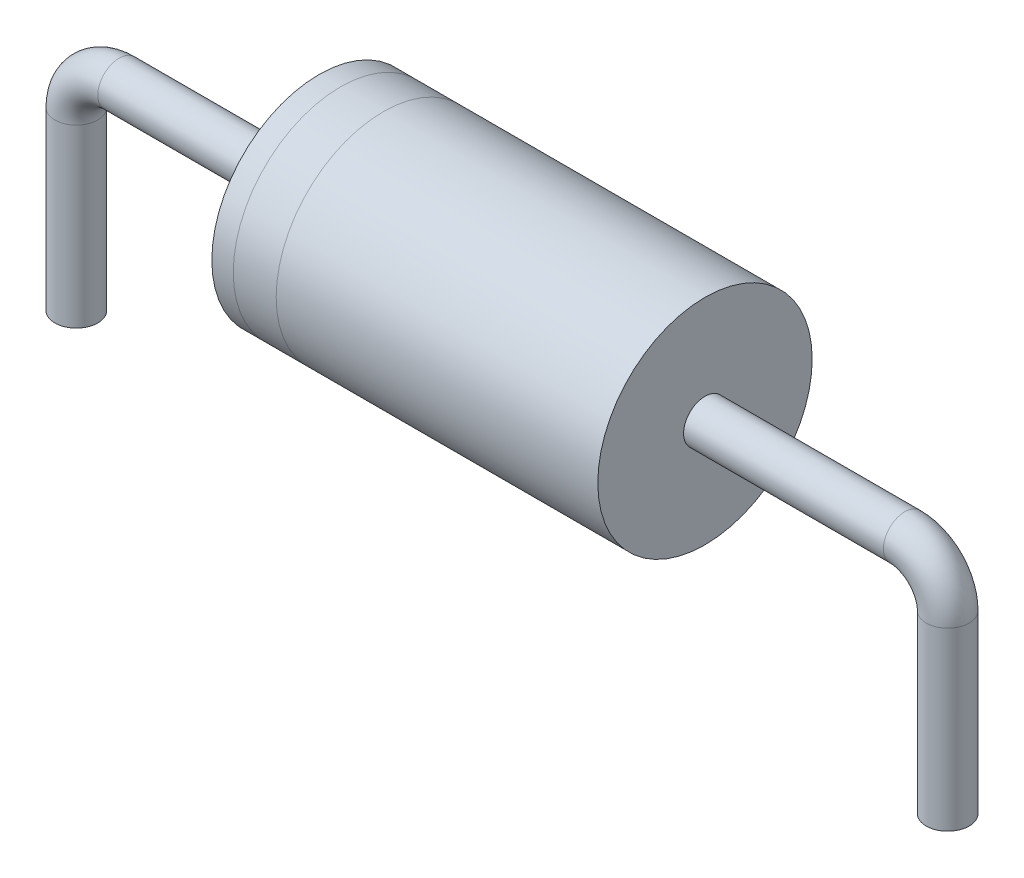
SolidWorks part; units mm, degrees
ref_plane "Спереди" through (0, 0, 0) normal (0, 0, 1) x (1, 0, 0)
ref_plane "Сверху" through (0, 0, 0) normal (0, 1, 0) x (1, 0, 0)
ref_plane "Справа" through (0, 0, 0) normal (1, 0, 0) x (0, 0, -1)
sketch "Эскиз1" plane through (0, 0, 0) normal (1, 0, 0) x (0, 0, -1)
  circle A0 centre (0, 0) radius 2.5
  dimension "D1" = 5
extrude "Бобышка-Вытянуть1" add sketch "Эскиз1" along normal blind 4.5 and the other way blind 4.5
sketch "Эскиз2" plane through (0, 0, 0) normal (0, 0, 1) x (1, 0, 0)
  line L0 (-9.16, 0) -> (9.16, 0)
  line L1 (10.16, -1) -> (10.16, -5.1)
  line L2 (0, -50) -> (0, 50) construction
  line L3 (-10.16, -1) -> (-10.16, -5.1)
  arc A0 (9.16, 0) -> (10.16, -1) centre (9.16, -1) cw
  arc A1 (-9.16, 0) -> (-10.16, -1) centre (-9.16, -1) ccw
  point P8 (0, 0)
  point P9 (10.16, 0)
  point P11 (0, 0)
  dimension "D2" = 1
  dimension "D1" = 10.16
  dimension "D3" = 5.1
sketch "Эскиз3" plane through (4.5, 0, 0) normal (1, 0, 0) x (0, 0, -1)
  circle A0 centre (0, 0) radius 0.5
sweep "По траектории1" add profiles "Эскиз3" path "Эскиз2"
sketch "Эскиз4" plane through (0, 0, 0) normal (0, 0, 1) x (1, 0, 0)
  line L1 (-4, 7.854) -> (-3, 7.854)
  line L2 (-4, 7.854) -> (-4, -7.854)
  line L3 (-4, -7.854) -> (-3, -7.854)
  line L4 (-3, 7.854) -> (-3, -7.854)
  dimension "D1" = 15.708
wrap "Перенос1" sketch "Эскиз4" wrap type scribe source sketch "Эскиз4" face at (-4.5, 0, -2.5)
